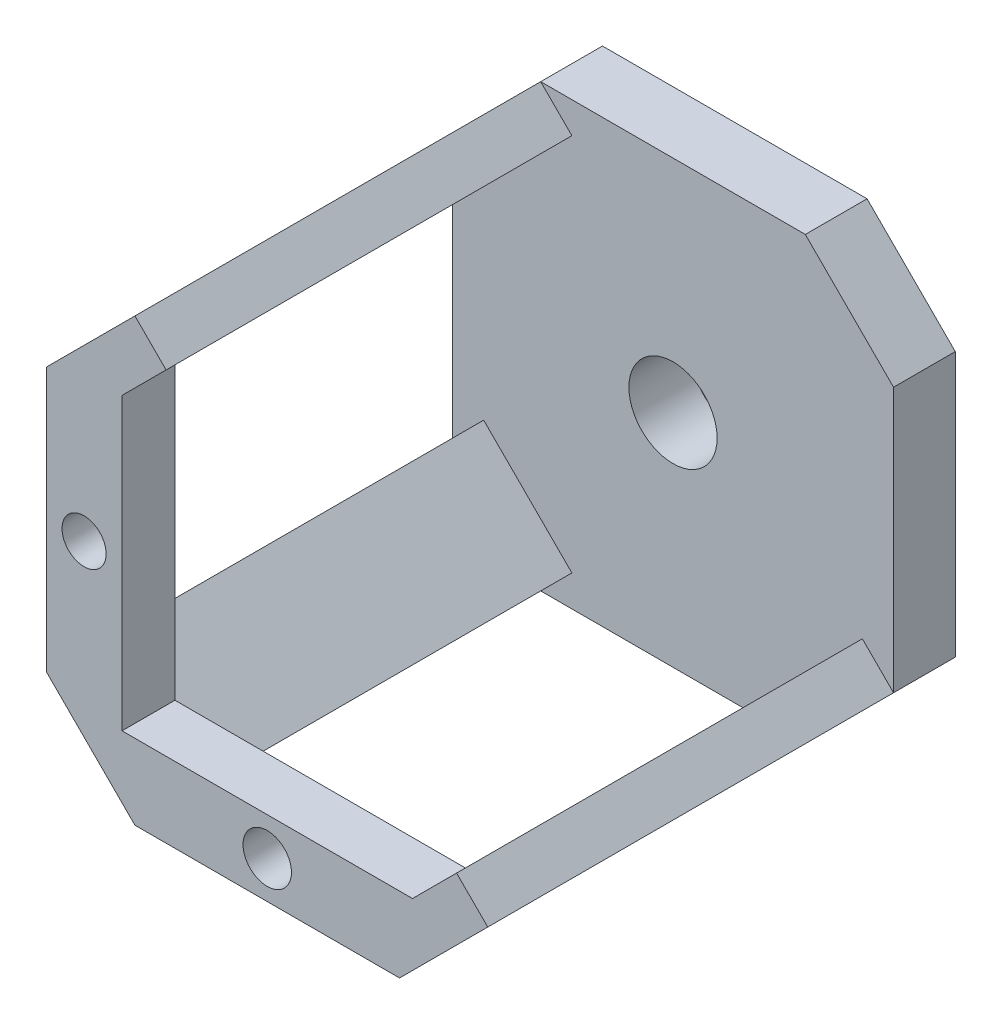
SolidWorks part; units mm, degrees
ref_plane "Plan de face" through (0, 0, 0) normal (0, 0, 1) x (1, 0, 0)
ref_plane "Plan de dessus" through (0, 0, 0) normal (0, 1, 0) x (1, 0, 0)
ref_plane "Plan de droite" through (0, 0, 0) normal (1, 0, 0) x (0, 0, -1)
sketch "Esquisse1" plane through (0, 0, 0) normal (0, 0, 1) x (1, 0, 0)
  line L1 (-26.8836, 22.9873) -> (23.1164, 22.9873)
  line L2 (-26.8836, 22.9873) -> (-26.8836, -27.0127)
  line L3 (-26.8836, -27.0127) -> (23.1164, -27.0127)
  line L4 (23.1164, 22.9873) -> (23.1164, -27.0127)
  dimension "D1" = 50
  dimension "D2" = 50
extrude "Boss.-Extru.1" add sketch "Esquisse1" along normal blind 7 contours L3 L4 L1 L2
chamfer "Chanfrein1" distance 10 angle 45 4 edges at (-26.8836, 22.9873, 3.5) (23.1164, 22.9873, 3.5) (-26.8836, -27.0127, 3.5) (23.1164, -27.0127, 3.5)
sketch "Esquisse2" plane through (0, 0, 7) normal (0, 0, 1) x (1, 0, 0)
  line L0 (-26.8836, -17.0127) -> (-16.8836, -27.0127)
  line L1 (-16.8836, -27.0127) -> (-13.348, -23.4772)
  line L2 (-13.348, -23.4772) -> (-23.348, -13.4772)
  line L3 (-23.348, -13.4772) -> (-26.8836, -17.0127)
  line L4 (-26.8836, 12.9873) -> (-16.8836, 22.9873)
  line L5 (-16.8836, 22.9873) -> (-13.348, 19.4518)
  line L6 (-13.348, 19.4518) -> (-23.348, 9.4518)
  line L7 (-23.348, 9.4518) -> (-26.8836, 12.9873)
  line L8 (23.1164, -17.0127) -> (19.5809, -13.4772)
  line L9 (19.5809, -13.4772) -> (9.5809, -23.4772)
  line L10 (9.5809, -23.4772) -> (13.1164, -27.0127)
  line L11 (-16.8836, -27.0127) -> (13.1164, -27.0127) construction
  line L12 (13.1164, -27.0127) -> (23.1164, -17.0127) construction
  line L13 (13.1164, -27.0127) -> (23.1164, -17.0127)
  line M8 (-16.8836, 22.9873) -> (-26.8836, 12.9873)
  line M12 (13.1164, -27.0127) -> (23.1164, -17.0127)
  dimension "D1" = 5
  dimension "D2" = 5
  dimension "D3" = 5
  dimension "D4" = 5
  dimension "D5" = 5
  dimension "D6" = 5
extrude "Boss.-Extru.2" add sketch "Esquisse2" along normal blind 40 contours L7 L6 L5 M8 | L9 L10 L8 M12 | L2 L3 L0 L1 region at (-20.1158, 16.2195, 7) region at (16.3487, -20.2449, 7)
ref_plane "Plan1" through (0, 0, 47) normal (0, 0, 1) x (1, 0, 0)
sketch "Esquisse4" plane through (0, 0, 47) normal (0, 0, 1) x (1, 0, 0)
  line L0 (-18.348, 14.4518) -> (-13.348, 19.4518)
  line L1 (-13.348, 19.4518) -> (-23.348, 9.4518) construction
  line L2 (-13.348, 19.4518) -> (-16.8836, 22.9873)
  line L3 (-16.8836, 22.9873) -> (-26.8836, 12.9873)
  line L4 (-26.8836, 12.9873) -> (-26.8836, -17.0127)
  line L5 (-26.8836, -17.0127) -> (-16.8836, -27.0127)
  line L6 (-16.8836, -27.0127) -> (13.1164, -27.0127)
  line L7 (13.1164, -27.0127) -> (23.1164, -17.0127)
  line L8 (23.1164, -17.0127) -> (19.5809, -13.4772)
  line L9 (19.5809, -13.4772) -> (14.5809, -18.4772)
  line L10 (19.5809, -13.4772) -> (9.5809, -23.4772) construction
  line L11 (14.5809, -18.4772) -> (-18.348, -18.4772)
  line L12 (-13.348, -23.4772) -> (-23.348, -13.4772) construction
  line L13 (-18.348, -18.4772) -> (-18.348, 14.4518)
extrude "Boss.-Extru.3" add sketch "Esquisse4" along normal blind 6
sketch "Esquisse5" plane through (0, 0, 0) normal (0, 0, -1) x (-1, 0, 0)
  line L0 (-23.1164, 12.9873) -> (-23.1164, -17.0127) construction
  line L1 (16.8836, 22.9873) -> (-13.1164, 22.9873) construction
  circle A0 centre (1.8836, -2.0127) radius 5
  point P2 (-23.1164, -2.0127)
  dimension "D3" = 10
  dimension "D1" = 25
  dimension "D2" = 25
extrude "Enlèv. mat.-Extru.1" cut sketch "Esquisse5" against normal up to surface (7 mm away) contours A0 up to face at (-4.2356, -4.3648, 7)
sketch "Esquisse6" plane through (0, 0, 53) normal (0, 0, 1) x (1, 0, 0)
  line L0 (-18.348, -18.4772) -> (-18.348, 14.4518) construction
  line L2 (14.5809, -18.4772) -> (-18.348, -18.4772) construction
  line L3 (-26.8836, 12.9873) -> (-26.8836, -17.0127) construction
  line L4 (23.1164, 12.9873) -> (23.1164, -17.0127) construction
  line L5 (-16.8836, -27.0127) -> (13.1164, -27.0127) construction
  circle A0 centre (-22.648, -2.0127) radius 2.5
  circle A1 centre (-1.8836, -22.7772) radius 2.745
  dimension "D3" = 5
  dimension "D1" = 4.3
  dimension "D2" = 4.3
  dimension "D4" = 25
  dimension "D5" = 25
  dimension "D6" = 25
  dimension "D7" = 4.2355
  dimension "D8" = 4.2355
extrude "Enlèv. mat.-Extru.2" cut sketch "Esquisse6" against normal up to surface (6 mm away) up to face at (-22.4432, -4.3401, 47)
